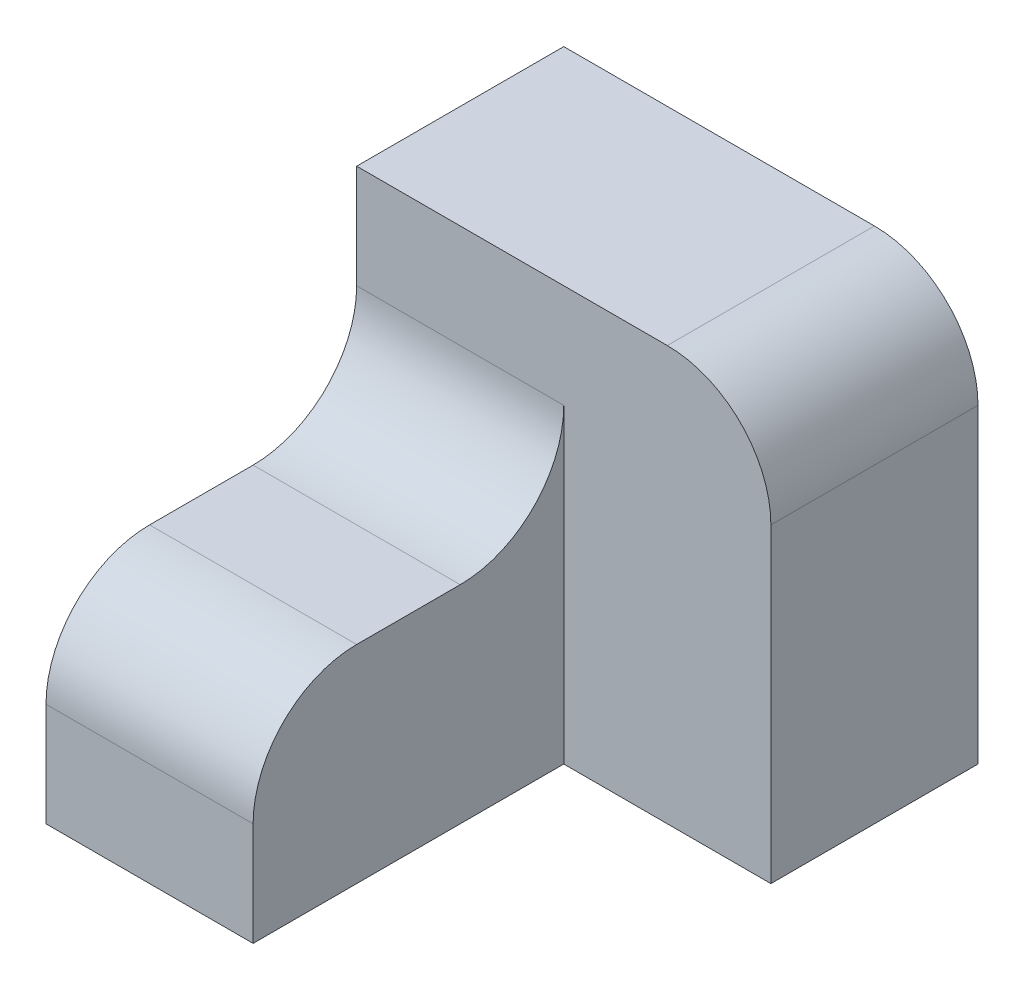
SolidWorks part; units mm, degrees
ref_plane "前基準面" through (0, 0, 0) normal (0, 0, 1) x (1, 0, 0)
ref_plane "上基準面" through (0, 0, 0) normal (0, 1, 0) x (1, 0, 0)
ref_plane "右基準面" through (0, 0, 0) normal (1, 0, 0) x (0, 0, -1)
sketch "草圖1" plane through (0, 0, 0) normal (0, 1, 0) x (1, 0, 0)
  line L0 (0, 0) -> (20, 0)
  line L1 (20, 0) -> (20, 30)
  line L2 (20, 30) -> (40, 30)
  line L3 (40, 30) -> (40, 50)
  line L4 (40, 50) -> (0, 50)
  line L5 (0, 50) -> (0, 0)
  line L6 (20, 30) -> (0, 30)
  dimension "D1" = 20
  dimension "D2" = 30
  dimension "D3" = 20
  dimension "D4" = 20
extrude "填料-伸長1" add sketch "草圖1" along normal blind 20 contours L1 L6 L5 L0 region at (10, 0, -15)
extrude "填料-伸長2" add sketch "草圖1<3>" along normal blind 40 contours L6 L2 L3 L4 L5 region at (20, 0, -40)
sketch "草圖1<3>" plane through (0, 0, 0) normal (0, 1, 0) x (1, 0, 0) same geometry as "草圖1"
fillet "圓角1" radius 10 3 edges at (40, 40, -40) (10, 20, 0) (10, 20, -30)
